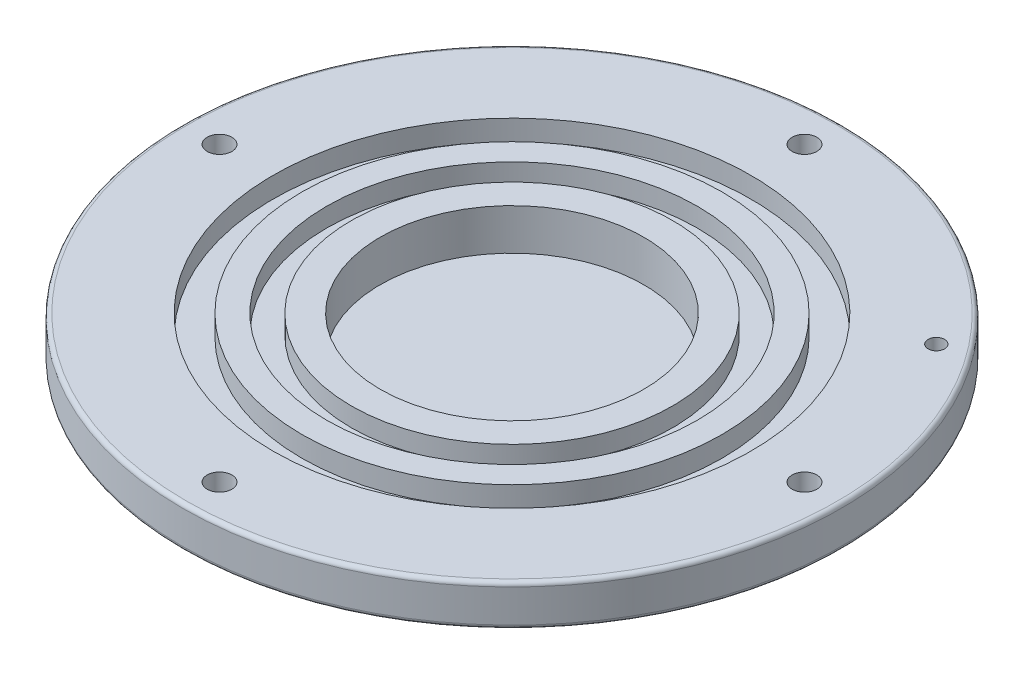
SolidWorks part; units mm, degrees
ref_plane "Front Plane" through (0, 0, 0) normal (0, 0, 1) x (1, 0, 0)
ref_plane "Top Plane" through (0, 0, 0) normal (0, 1, 0) x (1, 0, 0)
ref_plane "Right Plane" through (0, 0, 0) normal (1, 0, 0) x (0, 0, -1)
sketch "Sketch1" plane through (0, 0, 0) normal (0, 1, 0) x (1, 0, 0)
  line L0 (-40, 0) -> (40, 0) construction
  line L1 (0, 40) -> (0, -40) construction
  circle A0 centre (0, 0) radius 16
  circle A1 centre (0, 0) radius 19.5
  circle A2 centre (0, 0) radius 22.5
  circle A3 centre (0, 0) radius 25.5
  circle A4 centre (0, 0) radius 29
  circle A5 centre (0, 0) radius 40
  circle A6 centre (35.5, 0) radius 1.5
  circle A7 centre (0, -35.5) radius 1.5
  circle A8 centre (-35.5, 0) radius 1.5
  circle A9 centre (0, 35.5) radius 1.5
  point P23 (0, 0)
  dimension "D1" = 32
  dimension "D2" = 3
  dimension "D3" = 3.5
  dimension "D4" = 3
  dimension "D5" = 3.5
  dimension "D6" = 11
  dimension "D7" = 3
  dimension "D8" = 35.5
  dimension "D9" = 4
sketch "Sketch2" plane through (0, 0, 0) normal (0, 1, 0) x (1, 0, 0)
  circle A0 centre (0, 0) radius 40
  dimension "D1" = 80
extrude "Boss-Extrude11" add sketch "Sketch1" against normal blind 5 contours A5
extrude "Cut-Extrude5" cut sketch "Sketch1<14>" against normal through all contours A6 | A9 | A7 | A8
sketch "Sketch1<14>" plane through (0, 0, 0) normal (0, 1, 0) x (1, 0, 0) same geometry as "Sketch1"
sketch "offsetCircle" plane through (0, 0, 0) normal (0, 1, 0) x (1, 0, 0)
  line L0 (-22.5, 0) -> (22.5, 0) construction
  line L1 (-40, 0) -> (40, 0) construction
  circle A1 centre (0, 0) radius 22.5 construction
  circle A2 centre (0, 0) radius 22.5
extrude "Boss-Extrude14" add sketch "offsetCircle" against normal blind 10
extrude "Cut-Extrude6" cut sketch "Sketch1<15>" against normal blind 2.3 contours A2 | A1
sketch "Sketch1<15>" plane through (0, 0, 0) normal (0, 1, 0) x (1, 0, 0) same geometry as "Sketch1"
extrude "Cut-Extrude7" cut sketch "Sketch1<16>" against normal blind 2.5 contours A4 | A3
sketch "Sketch1<16>" plane through (0, 0, 0) normal (0, 1, 0) x (1, 0, 0) same geometry as "Sketch1"
sketch "Sketch10" plane through (0, 0, 0) normal (0, 1, 0) x (1, 0, 0)
  line L0 (0, 22.5) -> (33.0719, 22.5) construction
  line L1 (0, 40) -> (0, -40) construction
  line L2 (29, 0) -> (29, 27.55) construction
  line L3 (-40, 0) -> (40, 0) construction
  circle A0 centre (0, 0) radius 22.5 construction
  circle A1 centre (0, 0) radius 40 construction
  circle A2 centre (0, 0) radius 29 construction
  circle A3 centre (29, 22.5) radius 1
  dimension "D1" = 2
extrude "Cut-Extrude8" cut sketch "Sketch10" against normal through all
extrude "Cut-Extrude9" cut sketch "Sketch1<17>" against normal blind 5 contours A0
sketch "Sketch1<17>" plane through (0, 0, 0) normal (0, 1, 0) x (1, 0, 0) same geometry as "Sketch1"
fillet "Fillet1" radius 0.5 1 edges at (0, -5, 40)
fillet "Fillet2" radius 0.5 1 edges at (0, 0, 40)
fillet "Fillet3" radius 0.5 1 edges at (0, -10, 22.5)
